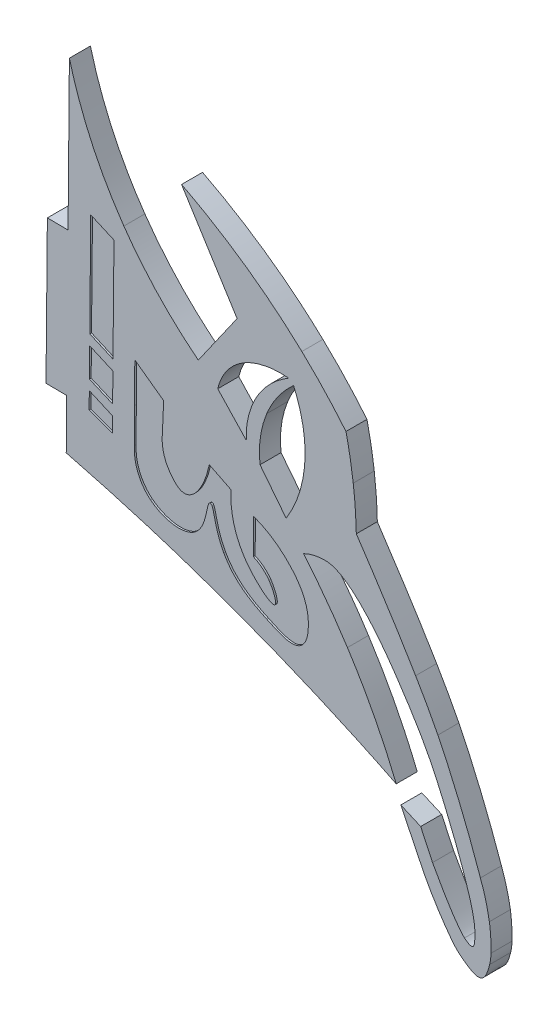
SolidWorks part; units mm, degrees
ref_plane "Front Plane" through (0, 0, 0) normal (0, 0, 1) x (1, 0, 0)
ref_plane "Top Plane" through (0, 0, 0) normal (0, 1, 0) x (1, 0, 0)
ref_plane "Right Plane" through (0, 0, 0) normal (1, 0, 0) x (0, 0, -1)
sketch "Model" plane through (0, 0, 0) normal (0, 0, 1) x (1, 0, 0)
  spline S0 degree 3 poles (88.7879, 92.3649) (92.085, 87.4641) (99.3472, 76.5434) (105.73, 65.7448) knots 0 0 0 0 1 1 1 1
  spline S1 degree 3 poles (105.73, 65.7448) (107.9017, 62.0708) (109.7378, 58.8112) (112.0814, 54.2401) knots 0 0 0 0 1 1 1 1
  spline S2 degree 3 poles (112.0814, 54.2401) (112.0814, 54.2401) (118.1856, 42.3344) (124.2285, 24.9794) knots 0 0 0 0 1 1 1 1
  spline S3 degree 3 poles (124.2285, 24.9794) (125.6666, 21.1424) (126.3947, 17.8541) (126.7888, 15.4333) knots 0 0 0 0 1 1 1 1
  spline S4 degree 3 poles (126.7888, 15.4333) (126.8711, 14.9278) (127.3681, 11.7793) (127.2475, 7.8602) knots 0 0 0 0 1 1 1 1
  spline S5 degree 3 poles (127.2475, 7.8602) (127.2191, 6.9352) (127.1574, 6.0059) (126.8655, 4.8665) knots 0 0 0 0 1 1 1 1
  spline S6 degree 3 poles (126.8655, 4.8665) (126.4946, 3.4189) (125.8625, 0.9176) (124.394, 0.3182) knots 0 0 0 0 1 1 1 1
  spline S7 degree 3 poles (124.394, 0.3182) (122.928, -0.2801) (121.075, 1.089) (119.4537, 2.2373) knots 0 0 0 0 1 1 1 1
  spline S8 degree 3 poles (119.4537, 2.2373) (117.5566, 3.5809) (116.4681, 4.9845) (116.291, 5.2167) knots 0 0 0 0 1 1 1 1
  spline S9 degree 3 poles (116.291, 5.2167) (111.139, 11.9701) (108.1301, 18.0507) (108.1301, 18.0507) knots 0 0 0 0 1 1 1 1
  spline S10 degree 3 poles (108.1301, 18.0507) (105.1488, 24.1087) (102.8416, 28.8794) (101.5004, 31.6639) knots 0 0 0 0 1 1 1 1
  spline S11 degree 3 poles (101.5004, 31.6639) (103.3919, 30.8322) (105.2833, 30.0005) (107.1747, 29.1688) knots 0 0 0 0 1 1 1 1
  spline S12 degree 3 poles (107.1747, 29.1688) (108.6927, 25.9868) (109.857, 23.4572) (110.5518, 21.9344) knots 0 0 0 0 1 1 1 1
  spline S13 degree 3 poles (110.5518, 21.9344) (112.1242, 19.0511) (117.115, 10.0395) (119.6948, 7.8703) knots 0 0 0 0 1 1 1 1
  spline S14 degree 3 poles (119.6948, 7.8703) (120.1419, 7.4944) (121.2365, 6.574) (121.938, 6.8725) knots 0 0 0 0 1 1 1 1
  spline S15 degree 3 poles (121.938, 6.8725) (122.3745, 7.0583) (122.4851, 7.642) (122.5366, 7.9826) knots 0 0 0 0 1 1 1 1
  spline S16 degree 3 poles (122.5366, 7.9826) (123.0085, 11.1041) (122.2249, 14.5708) (121.9672, 15.6257) knots 0 0 0 0 1 1 1 1
  spline S17 degree 3 poles (121.9672, 15.6257) (121.6802, 16.8008) (121.4227, 17.7379) (121.247, 18.3572) knots 0 0 0 0 1 1 1 1
  spline S18 degree 3 poles (121.247, 18.3572) (120.7676, 20.047) (120.289, 21.4632) (119.6664, 23.2931) knots 0 0 0 0 1 1 1 1
  spline S19 degree 3 poles (119.6664, 23.2931) (118.6825, 26.1851) (117.8469, 28.3392) (117.0544, 30.3876) knots 0 0 0 0 1 1 1 1
  spline S20 degree 3 poles (117.0544, 30.3876) (115.6944, 33.9032) (114.5591, 36.5829) (114.0628, 37.7409) knots 0 0 0 0 1 1 1 1
  spline S21 degree 3 poles (114.0628, 37.7409) (112.4888, 41.4138) (110.9504, 44.7961) (109.9178, 46.8252) knots 0 0 0 0 1 1 1 1
  spline S22 degree 3 poles (109.9178, 46.8252) (107.6013, 51.3779) (104.5648, 56.5119) (99.7463, 63.5122) knots 0 0 0 0 1 1 1 1
  spline S23 degree 3 poles (99.7463, 63.5122) (87.9923, 80.588) (82.0254, 81.2572) (80.2038, 81.3367) knots 0 0 0 0 1 1 1 1
  spline S24 degree 3 poles (80.2038, 81.3367) (77.5123, 81.4541) (75.2427, 80.6604) (73.6978, 79.9331) knots 0 0 0 0 1 1 1 1
  spline S25 degree 3 poles (73.6978, 79.9331) (77.8136, 75.0517) (82.1005, 69.4066) (86.2587, 62.9679) knots 0 0 0 0 1 1 1 1
  spline S26 degree 3 poles (86.2587, 62.9679) (92.4895, 53.3201) (96.9531, 44.1796) (100.1851, 36.2237) knots 0 0 0 0 1 1 1 1
  spline S27 degree 3 poles (100.1851, 36.2237) (83.5098, 44.4791) (64.4114, 52.7122) (42.9679, 60.0189) knots 0 0 0 0 1 1 1 1
  spline S28 degree 3 poles (42.9679, 60.0189) (30.0471, 64.4215) (17.6579, 68.0165) (5.9514, 70.9625) knots 0 0 0 0 1 1 1 1
  spline S29 degree 3 poles (5.9514, 70.9625) (5.9961, 75.7174) (6.0409, 80.4723) (6.0856, 85.2272) knots 0 0 0 0 1 1 1 1
  spline S30 degree 3 poles (6.0856, 85.2272) (4.1149, 85.2458) (2.1442, 85.2644) (0.1734, 85.283) knots 0 0 0 0 1 1 1 1
  spline S31 degree 3 poles (0.1734, 85.283) (0.3024, 98.985) (0.4313, 112.687) (0.5602, 126.389) knots 0 0 0 0 1 1 1 1
  spline S32 degree 3 poles (0.5602, 126.389) (2.531, 126.3704) (4.5017, 126.3519) (6.4724, 126.3333) knots 0 0 0 0 1 1 1 1
  spline S33 degree 3 poles (6.4724, 126.3333) (6.5974, 140.5687) (6.7225, 154.804) (6.8475, 169.0394) knots 0 0 0 0 1 1 1 1
  spline S34 degree 3 poles (6.8475, 169.0394) (9.0401, 160.6742) (13.3813, 148.2418) (22.409, 135.2905) knots 0 0 0 0 1 1 1 1
  spline S35 degree 3 poles (22.409, 135.2905) (29.6779, 124.8626) (37.5784, 117.5509) (43.6628, 112.7499) knots 0 0 0 0 1 1 1 1
  spline S36 degree 3 poles (43.6628, 112.7499) (47.3564, 118.0255) (51.0499, 123.3011) (54.7435, 128.5767) knots 0 0 0 0 1 1 1 1
  spline S37 degree 3 poles (54.7435, 128.5767) (49.4561, 136.9888) (44.1688, 145.401) (38.8815, 153.8132) knots 0 0 0 0 1 1 1 1
  spline S38 degree 3 poles (38.8815, 153.8132) (49.0499, 148.5824) (61.3143, 140.8966) (73.2384, 129.6841) knots 0 0 0 0 1 1 1 1
  spline S39 degree 3 poles (73.2384, 129.6841) (78.1217, 125.0923) (82.2874, 120.5301) (85.8321, 116.1979) knots 0 0 0 0 1 1 1 1
  spline S40 degree 3 poles (85.8321, 116.1979) (86.6493, 112.6359) (87.3764, 108.7107) (87.9079, 104.4589) knots 0 0 0 0 1 1 1 1
  spline S41 degree 3 poles (87.9079, 104.4589) (88.4505, 100.1191) (88.7108, 96.0675) (88.7879, 92.3649) knots 0 0 0 0 1 1 1 1
  spline S42 degree 3 poles (57.3546, 99.788) (54.6433, 102.6765) (51.932, 105.5651) (49.2208, 108.4537) knots 0 0 0 0 1 1 1 1
  spline S43 degree 3 poles (49.2208, 108.4537) (49.6237, 110.1809) (50.6703, 113.4225) (53.6341, 116.2956) knots 0 0 0 0 1 1 1 1
  spline S44 degree 3 poles (53.6341, 116.2956) (59.663, 122.1399) (68.3355, 121.3319) (69.4816, 121.2075) knots 0 0 0 0 1 1 1 1
  spline S45 degree 3 poles (69.4816, 121.2075) (67.4326, 119.9995) (63.9205, 117.5669) (61.1594, 113.3718) knots 0 0 0 0 1 1 1 1
  spline S46 degree 3 poles (61.1594, 113.3718) (57.4048, 107.6673) (57.2695, 102.093) (57.3546, 99.788) knots 0 0 0 0 1 1 1 1
  spline S47 degree 3 poles (70.8624, 120.0902) (68.8372, 118.2678) (65.4258, 114.7196) (63.2081, 109.3034) knots 0 0 0 0 1 1 1 1
  spline S48 degree 3 poles (63.2081, 109.3034) (60.8173, 103.4645) (60.9987, 98.3483) (61.2913, 95.7018) knots 0 0 0 0 1 1 1 1
  spline S49 degree 3 poles (61.2913, 95.7018) (63.779, 92.529) (66.2668, 89.3563) (68.7545, 86.1835) knots 0 0 0 0 1 1 1 1
  spline S50 degree 3 poles (68.7545, 86.1835) (70.4846, 88.9858) (72.5287, 93.1017) (73.5398, 98.3471) knots 0 0 0 0 1 1 1 1
  spline S51 degree 3 poles (73.5398, 98.3471) (75.4631, 108.324) (72.5004, 116.4275) (70.8624, 120.0902) knots 0 0 0 0 1 1 1 1
  spline S52 degree 3 poles (19.5805, 130.4154) (17.3702, 131.3871) (15.1599, 132.3589) (12.9496, 133.3307) knots 0 0 0 0 1 1 1 1
  spline S53 degree 3 poles (12.9496, 133.3307) (12.8568, 123.4729) (12.7641, 113.6152) (12.6713, 103.7574) knots 0 0 0 0 1 1 1 1
  spline S54 degree 3 poles (12.6713, 103.7574) (14.8816, 102.7857) (17.092, 101.8139) (19.3023, 100.8422) knots 0 0 0 0 1 1 1 1
  spline S55 degree 3 poles (19.3023, 100.8422) (19.395, 110.6999) (19.4878, 120.5576) (19.5805, 130.4154) knots 0 0 0 0 1 1 1 1
  spline S56 degree 3 poles (19.2744, 97.8848) (17.0641, 98.8566) (14.8538, 99.8284) (12.6435, 100.8001) knots 0 0 0 0 1 1 1 1
  spline S57 degree 3 poles (12.6435, 100.8001) (12.6175, 98.0396) (12.5915, 95.2791) (12.5656, 92.5186) knots 0 0 0 0 1 1 1 1
  spline S58 degree 3 poles (12.5656, 92.5186) (14.7762, 91.5775) (16.9868, 90.6364) (19.1974, 89.6953) knots 0 0 0 0 1 1 1 1
  spline S59 degree 3 poles (19.1974, 89.6953) (19.2231, 92.4252) (19.2488, 95.155) (19.2744, 97.8848) knots 0 0 0 0 1 1 1 1
  spline S60 degree 3 poles (19.1696, 86.738) (16.9592, 87.7098) (14.7489, 88.6815) (12.5386, 89.6533) knots 0 0 0 0 1 1 1 1
  spline S61 degree 3 poles (12.5386, 89.6533) (12.5234, 88.037) (12.5082, 86.4208) (12.493, 84.8045) knots 0 0 0 0 1 1 1 1
  spline S62 degree 3 poles (12.493, 84.8045) (14.705, 84.01) (16.9169, 83.2154) (19.1289, 82.4209) knots 0 0 0 0 1 1 1 1
  spline S63 degree 3 poles (19.1289, 82.4209) (19.1425, 83.8599) (19.156, 85.299) (19.1696, 86.738) knots 0 0 0 0 1 1 1 1
  spline S64 degree 3 poles (68.2515, 76.6219) (70.1122, 74.8685) (74.8361, 70.4169) (75.0699, 63.9845) knots 0 0 0 0 1 1 1 1
  spline S65 degree 3 poles (75.0699, 63.9845) (75.1223, 62.5413) (75.2748, 58.347) (72.7513, 56.6877) knots 0 0 0 0 1 1 1 1
  spline S66 degree 3 poles (72.7513, 56.6877) (70.3385, 55.1011) (66.864, 56.7424) (63.2059, 58.4705) knots 0 0 0 0 1 1 1 1
  spline S67 degree 3 poles (63.2059, 58.4705) (59.9413, 60.0126) (54.257, 62.6189) (50.9277, 68.7198) knots 0 0 0 0 1 1 1 1
  spline S68 degree 3 poles (50.9277, 68.7198) (48.0162, 74.0552) (48.2578, 79.0704) (47.0877, 79.0733) knots 0 0 0 0 1 1 1 1
  spline S69 degree 3 poles (47.0877, 79.0733) (45.7626, 79.0766) (46.4921, 72.3948) (42.4991, 69.6437) knots 0 0 0 0 1 1 1 1
  spline S70 degree 3 poles (42.4991, 69.6437) (39.1626, 67.3449) (33.5809, 68.5133) (30.0586, 71.3522) knots 0 0 0 0 1 1 1 1
  spline S71 degree 3 poles (30.0586, 71.3522) (25.8008, 74.7838) (25.4536, 79.9298) (25.4077, 80.8248) knots 0 0 0 0 1 1 1 1
  spline S72 degree 3 poles (25.4077, 80.8248) (25.4038, 81.2206) (25.3984, 81.816) (25.3945, 82.5384) knots 0 0 0 0 1 1 1 1
  spline S73 degree 3 poles (25.3945, 82.5384) (25.3681, 87.3216) (25.4542, 90.8345) (25.464, 92.4211) knots 0 0 0 0 1 1 1 1
  spline S74 degree 3 poles (25.464, 92.4211) (25.4875, 96.2034) (25.5075, 99.9851) (25.5239, 103.7661) knots 0 0 0 0 1 1 1 1
  spline S75 degree 3 poles (25.5239, 103.7661) (28.2707, 101.7724) (31.0174, 99.7787) (33.7642, 97.785) knots 0 0 0 0 1 1 1 1
  spline S76 degree 3 poles (33.7642, 97.785) (33.644, 94.9699) (33.5237, 92.1549) (33.4035, 89.3398) knots 0 0 0 0 1 1 1 1
  spline S77 degree 3 poles (33.4035, 89.3398) (33.2881, 88.0735) (33.1155, 84.3319) (35.5747, 80.9685) knots 0 0 0 0 1 1 1 1
  spline S78 degree 3 poles (35.5747, 80.9685) (36.3526, 79.9046) (37.8061, 77.9166) (39.6232, 77.834) knots 0 0 0 0 1 1 1 1
  spline S79 degree 3 poles (39.6232, 77.834) (42.3586, 77.7096) (45.4855, 81.923) (46.8011, 88.4668) knots 0 0 0 0 1 1 1 1
  spline S80 degree 3 poles (46.8011, 88.4668) (48.8539, 87.4453) (50.9068, 86.4238) (52.9596, 85.4023) knots 0 0 0 0 1 1 1 1
  spline S81 degree 3 poles (52.9596, 85.4023) (52.8389, 81.9244) (53.2031, 76.0164) (56.8509, 70.5367) knots 0 0 0 0 1 1 1 1
  spline S82 degree 3 poles (56.8509, 70.5367) (59.72, 66.2265) (64.482, 62.3894) (65.4997, 63.1364) knots 0 0 0 0 1 1 1 1
  spline S83 degree 3 poles (65.4997, 63.1364) (66.2304, 63.6728) (65.1159, 66.6339) (63.8618, 68.4063) knots 0 0 0 0 1 1 1 1
  spline S84 degree 3 poles (63.8618, 68.4063) (62.3798, 70.5009) (60.4585, 71.5427) (59.396, 72.0178) knots 0 0 0 0 1 1 1 1
  spline S85 degree 3 poles (59.396, 72.0178) (59.4273, 75.3485) (59.4586, 78.6791) (59.49, 82.0098) knots 0 0 0 0 1 1 1 1
  spline S86 degree 3 poles (59.49, 82.0098) (63.8111, 80.4076) (66.6552, 78.1262) (68.2515, 76.6219) knots 0 0 0 0 1 1 1 1
extrude "Boss-Extrude1" add sketch "Model" along normal blind 5.5 contours S54 S55 S52 S53 | S58 S59 S56 S57 | S62 S63 S60 S61 | S41 S40 S39 S38 S37 S36 S35 S34 S33 S32 S31 S30 S29 S28 S27 S26 S25 S24 S23 S22 S21 S20 S19 S18 S17 S16 S15 S14 S13 S12 S11 S10 S9 S8 S7 S6 S5 S4 S3 S2 S1 S0 S63 S62 S61 S60 S59 S58 S57 | S86 S85 S84 S83 S82 S81 S80 S79 S78 S77 S76 S75 S74 S73 S72 S71 S70 S69 S68 S67 S66 S65 S64 region at (53.7587, 90.7129, 0) region at (16.1259, 117.0864, 0) region at (15.914, 95.2274, 0) region at (15.7684, 85.9298, 0) region at (48.4325, 75.8453, 0)
extrude "Boss-Extrude2" add sketch "Model<3>" along normal blind 6
sketch "Model<3>" plane through (0, 0, 0) normal (0, 0, 1) x (1, 0, 0) same geometry as "Model"
